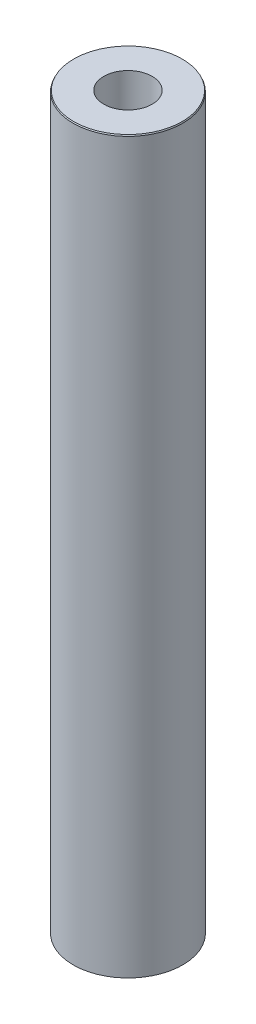
SolidWorks part; units mm, degrees
ref_plane "Front Plane" through (0, 0, 0) normal (0, 0, 1) x (1, 0, 0)
ref_plane "Top Plane" through (0, 0, 0) normal (0, 1, 0) x (1, 0, 0)
ref_plane "Right Plane" through (0, 0, 0) normal (1, 0, 0) x (0, 0, -1)
sketch "Sketch1" plane through (0, 0, 0) normal (0, 1, 0) x (1, 0, 0)
  circle A0 centre (0, 0) radius 45
  dimension "SHAFT_OD" = 90
extrude "Boss-Extrude1" add sketch "Sketch1" along normal blind 600
sketch "Sketch2" plane through (0, 0, 0) normal (0, 1, 0) x (1, 0, 0)
  circle A0 centre (0, 0) radius 19.8654
  dimension "BORE_D" = 39.7308
extrude "Cut-Extrude1" cut sketch "Sketch2" along normal through all
chamfer "Chamfer1" distance 0.9955 angle 25.246 2 edges at (0, 600, 45) (0, 0, 45) first distance on face at (0, 600, 45) first distance on face at (0, 0, 19.8654)
